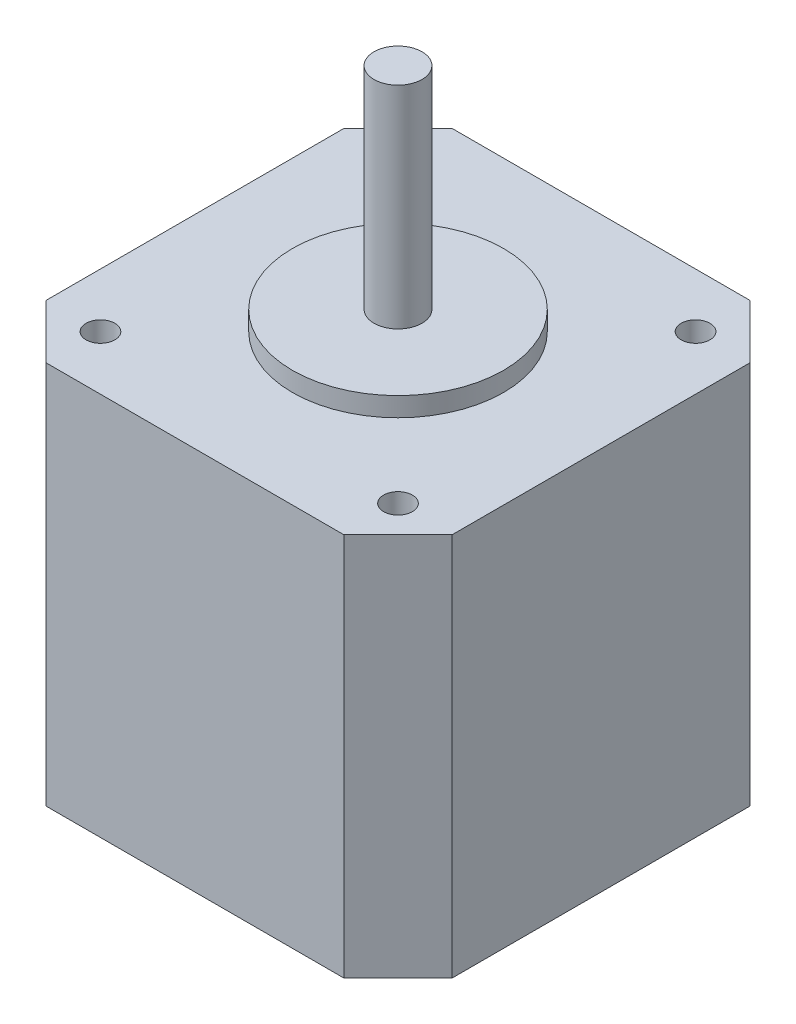
SolidWorks part; units mm, degrees
ref_plane "Front Plane" through (0, 0, 0) normal (0, 0, 1) x (1, 0, 0)
ref_plane "Top Plane" through (0, 0, 0) normal (0, 1, 0) x (1, 0, 0)
ref_plane "Right Plane" through (0, 0, 0) normal (1, 0, 0) x (0, 0, -1)
sketch "Sketch1" plane through (0, 0, 0) normal (0, 1, 0) x (1, 0, 0)
  line L0 (0, 0) -> (-12.9419, 0) construction
  line L1 (-15.5, -21.15) -> (15.5, -21.15)
  line L2 (-21.15, -15.5) -> (-21.15, 15.5)
  line L3 (-15.5, 21.15) -> (15.5, 21.15)
  line L4 (21.15, -15.5) -> (21.15, 15.5)
  line L5 (-21.15, -21.15) -> (21.15, 21.15) construction
  line L6 (-21.15, 21.15) -> (21.15, -21.15) construction
  line L7 (-21.15, 15.5) -> (-15.5, 21.15)
  line L8 (15.5, 21.15) -> (21.15, 15.5)
  line L9 (15.5, -21.15) -> (21.15, -15.5)
  line L10 (-21.15, -15.5) -> (-15.5, -21.15)
  circle A0 centre (-15.5, 15.5) radius 1.5
  circle A1 centre (15.5, -15.5) radius 1.5
  circle A2 centre (15.5, 15.5) radius 1.5
  circle A3 centre (-15.5, -15.5) radius 1.5
  point P0 (0, 0)
  dimension "D3" = 3
  dimension "D1" = 42.3
  dimension "D2" = 31
extrude "Boss-Extrude1" add sketch "Sketch1" along normal blind 40
sketch "Sketch2" plane through (0, 40, 0) normal (0, 1, 0) x (1, 0, 0)
  circle A0 centre (0, 0) radius 11
  dimension "D1" = 22
extrude "Boss-Extrude2" add sketch "Sketch2" along normal blind 2
sketch "Sketch3" plane through (0, 42, 0) normal (0, 1, 0) x (1, 0, 0)
  circle A0 centre (0, 0) radius 2.5
  dimension "D1" = 5
extrude "Boss-Extrude3" add sketch "Sketch3" along normal blind 22
